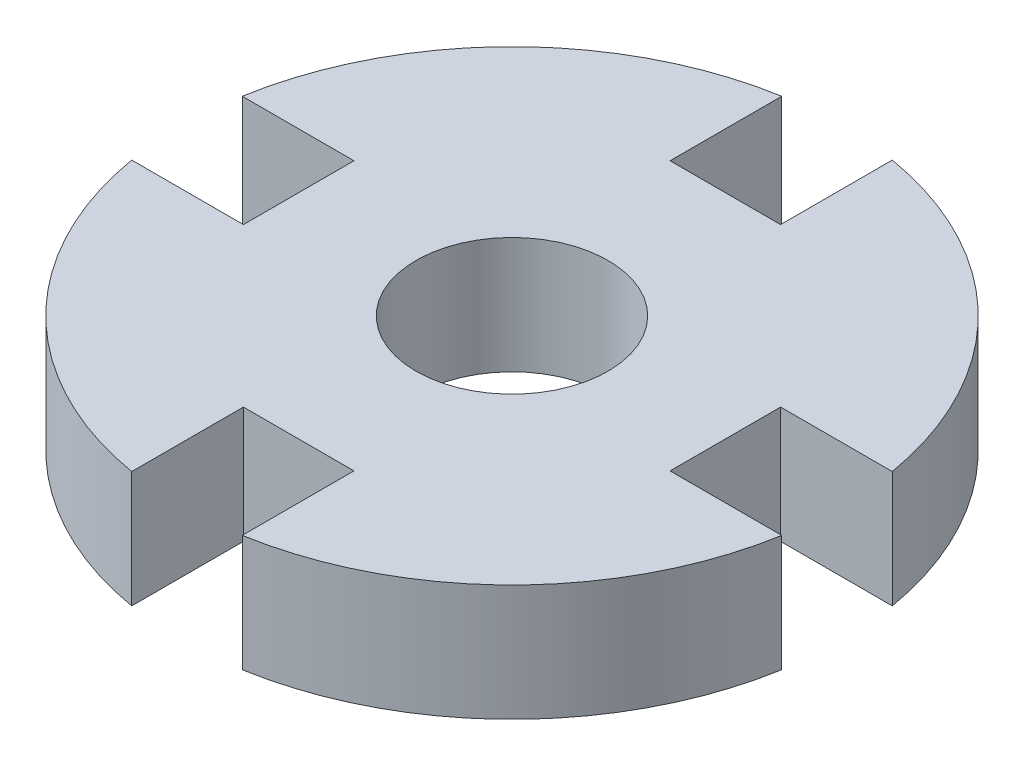
SolidWorks part; units mm, degrees
ref_plane "Front Plane" through (0, 0, 0) normal (0, 0, 1) x (1, 0, 0)
ref_plane "Top Plane" through (0, 0, 0) normal (0, 1, 0) x (1, 0, 0)
ref_plane "Right Plane" through (0, 0, 0) normal (1, 0, 0) x (0, 0, -1)
sketch "Sketch1" plane through (0, 0, 0) normal (0, 1, 0) x (1, 0, 0)
  circle A0 centre (0, 0) radius 8.5
  circle A1 centre (0, 0) radius 2.475
  circle A2 centre (0, 0) radius 2.475 construction
  point P8 (0, -8.5)
  dimension "D1" = 3
extrude "Boss-Extrude1" add sketch "Sketch1" along normal blind 1.5 and the other way blind 1.5
sketch "Sketch2" plane through (0, 1.5, 0) normal (0, 1, 0) x (1, 0, 0)
  line L0 (-8.5, 1.425) -> (-5.5, 1.425)
  line L1 (1.425, -8.5) -> (-1.425, -8.5)
  line L2 (1.425, -8.5) -> (1.425, -5.5)
  line L3 (1.425, -5.5) -> (-1.425, -5.5)
  line L4 (-1.425, -8.5) -> (-1.425, -5.5)
  line L5 (0, -5.5) -> (0, -8.5) construction
  line L6 (1.425, -7) -> (-1.425, -7) construction
  line L7 (-5.5, -1.425) -> (-5.5, 1.425)
  line L8 (-8.5, -1.425) -> (-5.5, -1.425)
  line L9 (-8.5, -1.425) -> (-8.5, 1.425)
  line L10 (1.425, 8.5) -> (1.425, 5.5)
  line L11 (-1.425, 5.5) -> (1.425, 5.5)
  line L12 (-1.425, 8.5) -> (-1.425, 5.5)
  line L13 (-1.425, 8.5) -> (1.425, 8.5)
  line L14 (8.5, -1.425) -> (5.5, -1.425)
  line L15 (5.5, 1.425) -> (5.5, -1.425)
  line L16 (8.5, 1.425) -> (5.5, 1.425)
  line L17 (8.5, 1.425) -> (8.5, -1.425)
  circle A0 centre (0, 0) radius 8.5 construction
  point P0 (0, -7)
  point P21 (0, 0)
  dimension "D1" = 0
  dimension "D2" = 2.85
  dimension "D3" = 4
extrude "Cut-Extrude1" cut sketch "Sketch2" against normal through all
